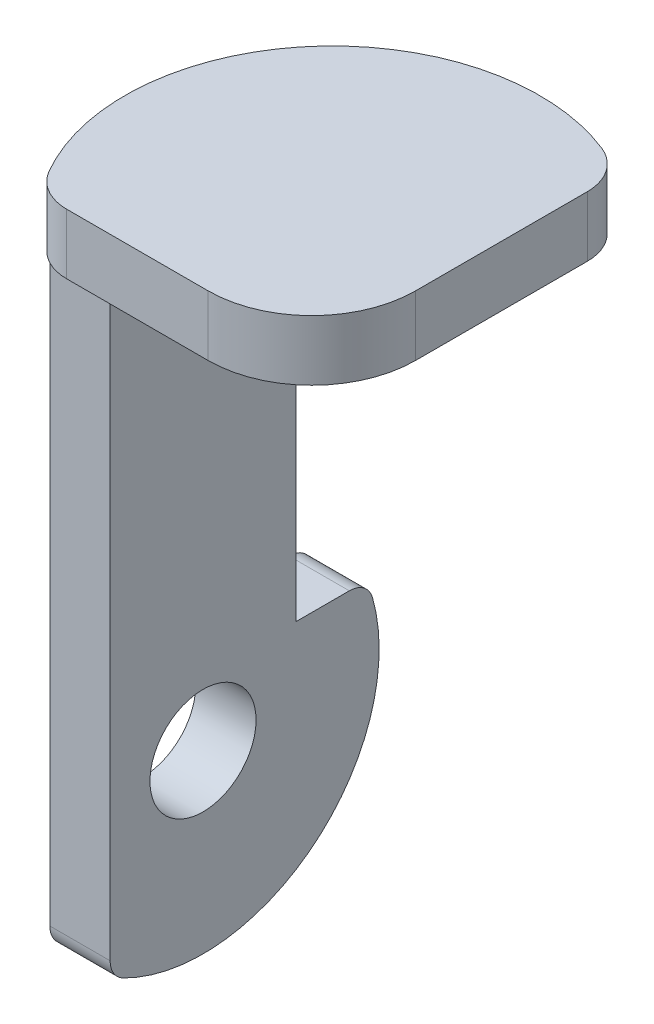
SolidWorks part; units mm, degrees
ref_plane "Front Plane" through (0, 0, 0) normal (0, 0, 1) x (1, 0, 0)
ref_plane "Top Plane" through (0, 0, 0) normal (0, 1, 0) x (1, 0, 0)
ref_plane "Right Plane" through (0, 0, 0) normal (1, 0, 0) x (0, 0, -1)
sketch "Sketch1" plane through (0, 0, 0) normal (0, 1, 0) x (1, 0, 0)
  line L2 (44.3666, 61.3373) -> (44.3666, -9.8544)
  line L3 (1.3666, -52.8544) -> (-57.2415, -52.8544)
  arc A0 (31.7504, 79.9244) -> (-74.5874, -42.8102) centre (0, 0) ccw
  arc A2 (1.3666, -52.8544) -> (44.3666, -9.8544) centre (1.3666, -9.8544) ccw
  arc A3 (44.3666, 61.3373) -> (31.7504, 79.9244) centre (24.3666, 61.3373) ccw
  arc A4 (-57.2415, -52.8544) -> (-74.5874, -42.8102) centre (-57.2415, -32.8544) cw
  dimension "D1" = 43
  dimension "D2" = 20
  dimension "D3" = 20
extrude "Boss-Extrude2" add sketch "Sketch1" against normal blind 25
ref_plane "Plane1" through (-75, 0, 0) normal (1, 0, 0) x (0, 0, -1)
sketch "Sketch2" plane through (-75, 0, 0) normal (1, 0, 0) x (0, 0, -1)
  line L0 (-42.1009, -215.3696) -> (-42.1009, -271.5545)
  line L2 (34.8991, -188.318) -> (34.8991, -25.3696)
  line L3 (34.8991, -25.3696) -> (-42.1009, -25.3696)
  line L4 (-42.1009, -215.3696) -> (-42.1009, -25.3696)
  line L8 (34.8991, -188.318) -> (57.0476, -188.318)
  circle A0 centre (-3.6009, -215.3696) radius 22
  arc A1 (-36.6247, -280.4728) -> (66.6744, -195.6114) centre (-3.6009, -215.3696) ccw
  arc A2 (-36.6247, -280.4728) -> (-42.1009, -271.5545) centre (-32.1009, -271.5545) cw
  arc A3 (66.6744, -195.6114) -> (57.0476, -188.318) centre (57.0476, -198.318) ccw
  point P0 (-3.6009, -120.3696)
extrude "Boss-Extrude5" add sketch "Sketch2" along normal blind 25 separate body
ref_point "Point1"
ref_axis "Axis1" through (0, 0, 0) along (0, -1, 0)
sketch "Sketch3" plane through (0, 0, 0) normal (0, 1, 0) x (1, 0, 0)
  line L0 (0, 0) -> (0, 38.7564)
